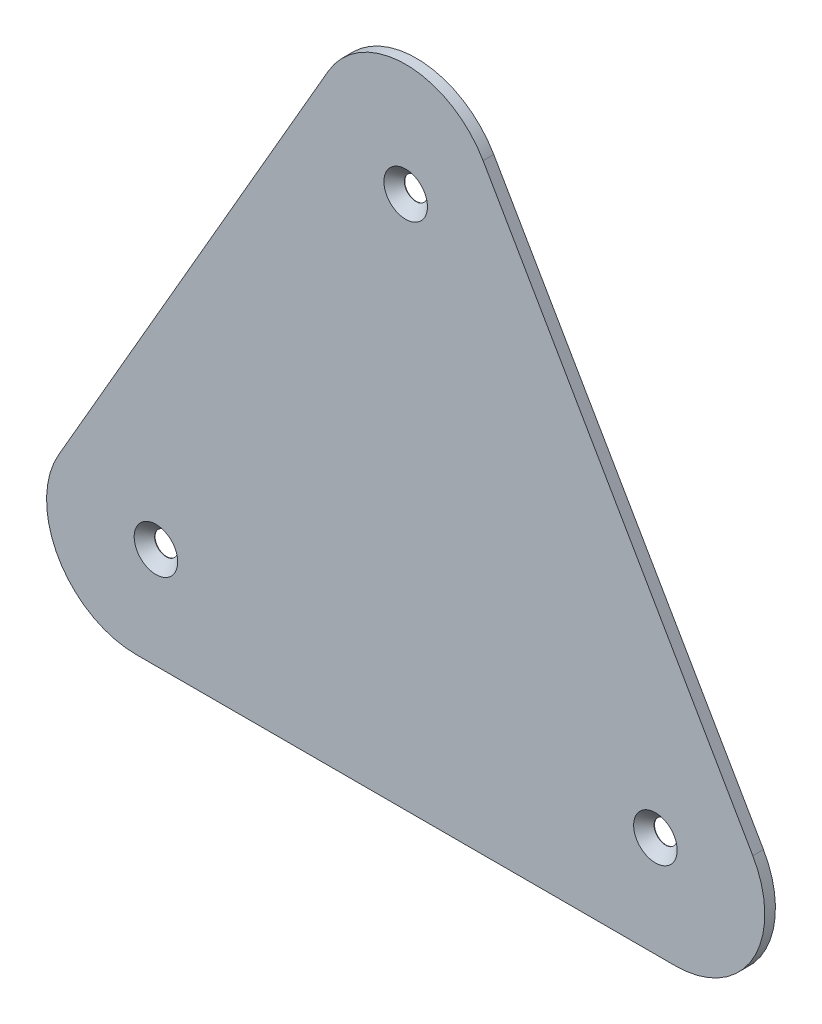
SolidWorks part; units mm, degrees
material "6061-T6 (SS)"
ref_plane "Front" through (0, 0, 0) normal (0, 0, 1) x (1, 0, 0)
ref_plane "Top" through (0, 0, 0) normal (0, 1, 0) x (1, 0, 0)
ref_plane "Right" through (0, 0, 0) normal (1, 0, 0) x (0, 0, -1)
sketch "Sketch1" plane through (0, 0, 0) normal (0, 0, 1) x (1, 0, 0)
  line L0 (-128.5875, -116.8675) -> (128.5875, -116.8675)
  line L1 (165.504, -52.9263) -> (36.9165, 169.7938)
  line L3 (-36.9165, 169.7938) -> (-165.504, -52.9263)
  line L4 (0, 148.4801) -> (0, 0) construction
  line L5 (0, 0) -> (-128.5875, -74.24) construction
  line L6 (0, 0) -> (128.5875, -74.24) construction
  arc A0 (128.5875, -116.8675) -> (165.504, -52.9263) centre (128.5875, -74.24) ccw
  arc A1 (36.9165, 169.7938) -> (-36.9165, 169.7938) centre (0, 148.4801) ccw
  arc A2 (-165.504, -52.9263) -> (-128.5875, -116.8675) centre (-128.5875, -74.24) ccw
  point P9 (0, 191.1075)
  dimension "D1" = 60
  dimension "D3" = 257.175
  dimension "D2" = 307.975
extrude "Boss-Extrude1" add sketch "Sketch1" along normal blind 5.08
sketch "Sketch2" plane through (0, 0, 5.08) normal (0, 0, 1) x (1, 0, 0)
  line L0 (0, 137.4815) -> (0, 0) construction
  line L1 (0, 148.4801) -> (0, 0) construction
  line L2 (0, 0) -> (-119.0625, -68.7408) construction
  line L3 (0, 0) -> (-128.5875, -74.24) construction
  line L4 (0, 0) -> (119.0625, -68.7408) construction
  line L5 (0, 0) -> (128.5875, -74.24) construction
  dimension "D1" = 238.125
hole_wizard "CSK for M10 Flat Head Machine Screw1" positions "Sketch4" profile "Sketch3" countersink size "M10" standard "ANSI Metric" end condition through all
sketch "Sketch4" plane through (0, 0, 5.08) normal (0, 0, 1) x (1, 0, 0)
  point P0 (0, 137.4815)
  point P3 (-119.0625, -68.7408)
  point P6 (119.0625, -68.7408)
sketch "Sketch3" plane through (0, 137.4815, 5.08) normal (1, 0, 0) x (0, -1, 0)
  line L0 (0, 0) -> (0, 5.08)
  line L1 (0, 5.08) -> (5.5, 5.08)
  line L2 (5.5, 5.08) -> (5.5, 4.881)
  line L3 (5.5, 4.881) -> (10.381, 0)
  line L5 (10.381, 0) -> (0, 0)
  line L6 (-5.5, 4.881) -> (-10.381, 0) construction
  line L11 (0, -6.35) -> (0, 107.95) construction
  dimension "Thru Hole Dia." = 11
  dimension "Thru Hole Depth" = 5.08
  dimension "Near C'Sink Dia." = 20.762
  dimension "Near C'Sink Angle" = 90
ref_axis "Axis2" through (0, 0, 0) along (0, 0, 1)
